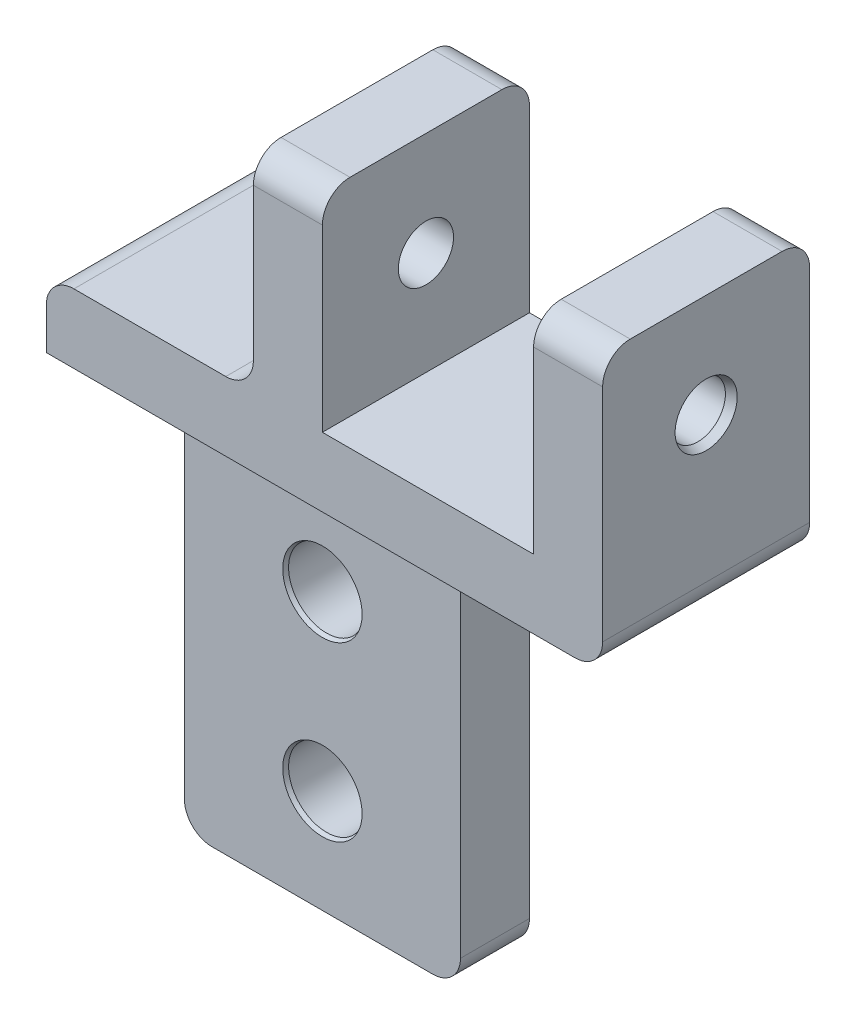
SolidWorks part; units mm, degrees
ref_plane "Front Plane" through (0, 0, 0) normal (0, 0, 1) x (1, 0, 0)
ref_plane "Top Plane" through (0, 0, 0) normal (0, 1, 0) x (1, 0, 0)
ref_plane "Right Plane" through (0, 0, 0) normal (1, 0, 0) x (0, 0, -1)
sketch "Sketch1" plane through (0, 0, 0) normal (1, 0, 0) x (0, 0, -1)
  line L0 (0, 20) -> (0, -20)
  line L1 (0, 20) -> (5, 20)
  line L2 (5, 20) -> (5, -20)
  line L3 (5, -20) -> (0, -20)
  line L4 (0, 20) -> (-10, 20)
  line L5 (-10, 20) -> (-10, 15)
  line L6 (-10, 15) -> (0, 15)
  point P4 (0, 0)
  dimension "D4" = 5
  dimension "D1" = 40
  dimension "D2" = 5
  dimension "D3" = 10
extrude "Boss-Extrude1" add sketch "Sketch1" along normal blind 20 contours L5 L6 L0 L4 | L3 L2 L1 L0 region at (0, 0, -2.5) region at (0, 17.5, 5)
sketch "Sketch3" plane through (20, 0, 0) normal (1, 0, 0) x (0, 0, -1)
  line L0 (-10, 20) -> (-10, 15)
  line L1 (-10, 15) -> (5, 15)
  line L2 (5, 20) -> (5, -20) construction
  line L3 (5, 15) -> (5, 20)
  line L4 (5, 20) -> (-10, 20)
extrude "Boss-Extrude2" add sketch "Sketch3" along normal blind 20.3
sketch "Sketch4" plane through (0, 20, 0) normal (0, 1, 0) x (1, 0, 0)
  line L0 (40.3, 5) -> (35.3, 5)
  line L1 (40.3, 5) -> (0, 5) construction
  line L2 (40.3, 5) -> (40.3, -10) construction
  line L3 (35.3, 5) -> (35.3, -10)
  line L4 (40.3, -10) -> (0, -10) construction
  line L5 (35.3, -10) -> (40.3, -10)
  line L6 (40.3, -10) -> (40.3, 5)
  line L7 (35.3, 5) -> (20, 5) construction
  line L8 (20, 5) -> (20, -10)
  line L9 (20, -10) -> (15, -10)
  line L10 (15, -10) -> (15, 5)
  line L11 (15, 5) -> (20, 5)
  line M2 (0, -10) -> (40.3, -10)
  line M4 (40.3, 5) -> (0, 5)
  dimension "D1" = 5
  dimension "D2" = 15.3
extrude "Boss-Extrude3" add sketch "Sketch4" along normal blind 15 contours L10 L8 M2 M4 | L3 L5 L6 L0 region at (17.5, 20, 2.5)
chamfer "Chamfer2" distance 7.5 angle 45 1 edges at (10, 15, 0)
fillet "Fillet1" radius 7.5 2 edges at (10, 15, 7.5) (20, 15, 1.25)
sketch "Sketch5" plane through (0, 0, 0) normal (0, 0, 1) x (1, 0, 0)
  line L0 (10, 7.5) -> (10, 0) construction
  line L1 (20, 7.5) -> (0, 7.5) construction
  line L2 (10, -20) -> (10, -12.5) construction
  line L3 (20, -20) -> (0, -20) construction
  dimension "D1" = 7.5
sketch "Sketch6" plane through (15, 0, 0) normal (-1, 0, 0) x (0, 0, 1)
  line L0 (2.5, 35) -> (2.5, 27.5) construction
  line L1 (10, 35) -> (-5, 35) construction
  point P1 (2.5, 27.5)
  dimension "D1" = 7.5
ref_plane "Plane1" through (27.65, 0, 0) normal (1, 0, 0) x (0, 0, -1)
hole_wizard "Ø4.0 (4) Diameter Hole1" positions "Sketch6" profile "Sketch7" hole size "Ø4.0" standard "ANSI Metric" end condition up to next
sketch "Sketch7" plane through (15, 27.5, 2.5) normal (0, 1, 0) x (0, 0, 1)
  line L0 (0, 0) -> (0, 5)
  line L1 (0, 5) -> (2, 5)
  line L2 (2, 5) -> (2, 0.6036)
  line L3 (2, 0.6036) -> (2.25, 0)
  line L5 (2.25, 0) -> (0, 0)
  line L6 (-2, 0.6036) -> (-2.25, 0) construction
  line L11 (0, -6.35) -> (0, 107.95) construction
  dimension "Thru Hole Dia." = 4
  dimension "Thru Hole Depth" = 5
  dimension "Near C'Sink Dia." = 4.5
  dimension "Near C'Sink Angle" = 45
mirror "Mirror1" about plane through (27.65, 0, 0) normal (1, 0, 0) of "Ø4.0 (4) Diameter Hole1"
hole_wizard "Ø5.5 (5.5) Diameter Hole1" positions "Sketch8" profile "Sketch9" hole size "Ø5.5" standard "ANSI Metric" end condition up to next
sketch "Sketch8" plane through (0, 0, 0) normal (0, 0, 1) x (1, 0, 0)
  point P0 (10, 0)
  point P3 (10, -12.5)
sketch "Sketch9" plane through (10, 0, 0) normal (1, 0, 0) x (0, -1, 0)
  line L0 (0, 0) -> (0, 5)
  line L1 (0, 5) -> (2.75, 5)
  line L2 (2.75, 5) -> (2.75, 0.3018)
  line L3 (2.75, 0.3018) -> (2.875, 0)
  line L5 (2.875, 0) -> (0, 0)
  line L6 (-2.75, 0.3018) -> (-2.875, 0) construction
  line L11 (0, -6.35) -> (0, 107.95) construction
  dimension "Thru Hole Dia." = 5.5
  dimension "Thru Hole Depth" = 5
  dimension "Near C'Sink Dia." = 5.75
  dimension "Near C'Sink Angle" = 45
fillet "Fillet2" radius 2 9 edges at (15, 20, 2.5) (0, 20, 2.5) (40.3, 15, 2.5) (20, -20, -2.5) (0, -20, -2.5) (37.8, 35, -5) (37.8, 35, 10) (17.5, 35, -5) (17.5, 35, 10)
